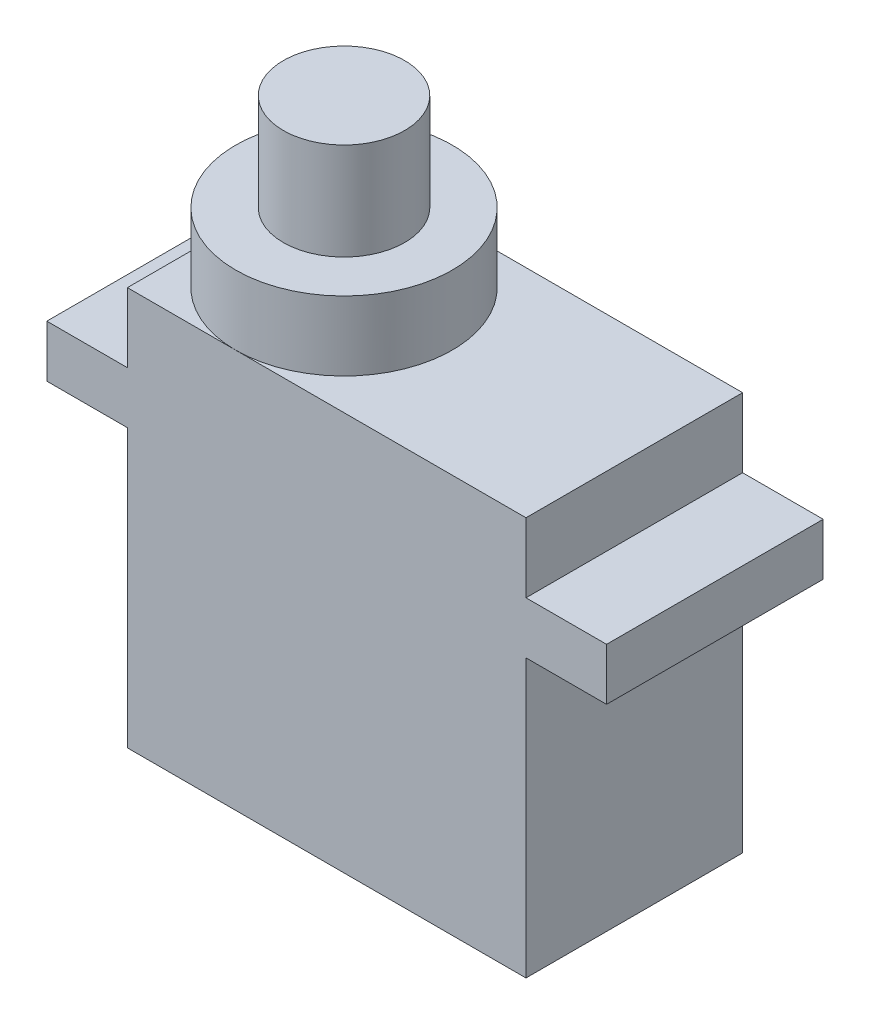
SolidWorks part; units mm, degrees
ref_plane "Płaszczyzna przednia" through (0, 0, 0) normal (0, 0, 1) x (1, 0, 0)
ref_plane "Płaszczyzna górna" through (0, 0, 0) normal (0, 1, 0) x (1, 0, 0)
ref_plane "Płaszczyzna prawa" through (0, 0, 0) normal (1, 0, 0) x (0, 0, -1)
sketch "Sketch1" plane through (0, 0, 0) normal (0, 1, 0) x (1, 0, 0)
  line L0 (-10.7409, 6.2842) -> (-15.3909, 6.2842)
  line L1 (-10.7409, 6.2842) -> (12.2591, 6.2842)
  line L2 (-10.7409, 6.2842) -> (-10.7409, -6.2158)
  line L3 (-10.7409, -6.2158) -> (12.2591, -6.2158)
  line L4 (12.2591, 6.2842) -> (12.2591, -6.2158)
  line L5 (-15.3909, 6.2842) -> (-15.3909, -6.2158)
  line L6 (-15.3909, -6.2158) -> (-10.7409, -6.2158)
  line L7 (12.2591, 6.2842) -> (16.9091, 6.2842)
  line L8 (16.9091, 6.2842) -> (16.9091, -6.2158)
  line L9 (16.9091, -6.2158) -> (12.2591, -6.2158)
  line L10 (0.7591, 13.3848) -> (0.7591, -13.6054) construction
  circle A0 centre (-4.4909, 0.0342) radius 6.25
  circle A1 centre (-4.4909, 0.0342) radius 3.5
  dimension "D4" = 7
  dimension "D1" = 12.5
  dimension "D2" = 23
  dimension "D3" = 32.3
extrude "Boss-Extrude1" add sketch "Sketch1" along normal blind 23 contours A0 L1 L2 | L10 A0 A1 | L1 L10 A0 L3 L4 | L10 A0 L3 | L10 L1 A0 | A0 L10 | A1 | A0 L2 L3 region at (-9.3448, 0, -4.8881) region at (-0.4859, 0, -5.4751) region at (-1.5832, 0, -5.3739) region at (-9.3448, 0, 4.8198) region at (6.6859, 0, -0.0342) region at (1.162, 0, -0.0342) region at (-0.4859, 0, 5.4068) region at (-4.4909, 0, -0.0342)
extrude "Boss-Extrude2" add sketch "Sketch1<3>" along normal blind 3 from offset 16 contours L5 L6 L2 L0 | L9 L8 L7 L4 region at (-13.0659, 0, -0.0342) region at (14.5841, 0, -0.0342)
sketch "Sketch1<3>" plane through (0, 0, 0) normal (0, 1, 0) x (1, 0, 0) same geometry as "Sketch1"
extrude "Boss-Extrude3" add sketch "Sketch1<4>" along normal blind 4 from surface contours A0 starting at face at (0.7591, 23, -0.0342)
sketch "Sketch1<4>" plane through (0, 0, 0) normal (0, 1, 0) x (1, 0, 0) same geometry as "Sketch1"
extrude "Boss-Extrude4" add sketch "Sketch1<5>" along normal blind 5.6 from surface contours A1 starting at face at (-4.4909, 27, 6.2158)
sketch "Sketch1<5>" plane through (0, 0, 0) normal (0, 1, 0) x (1, 0, 0) same geometry as "Sketch1"
sketch "Sketch2" plane through (0, 32.6, 0) normal (0, 1, 0) x (1, 0, 0)
  point P0 (-4.4909, 0.0342)
ref_plane "Plane1" through (-4.4909, 0, 0) normal (1, 0, 0) x (0, 0, -1)
